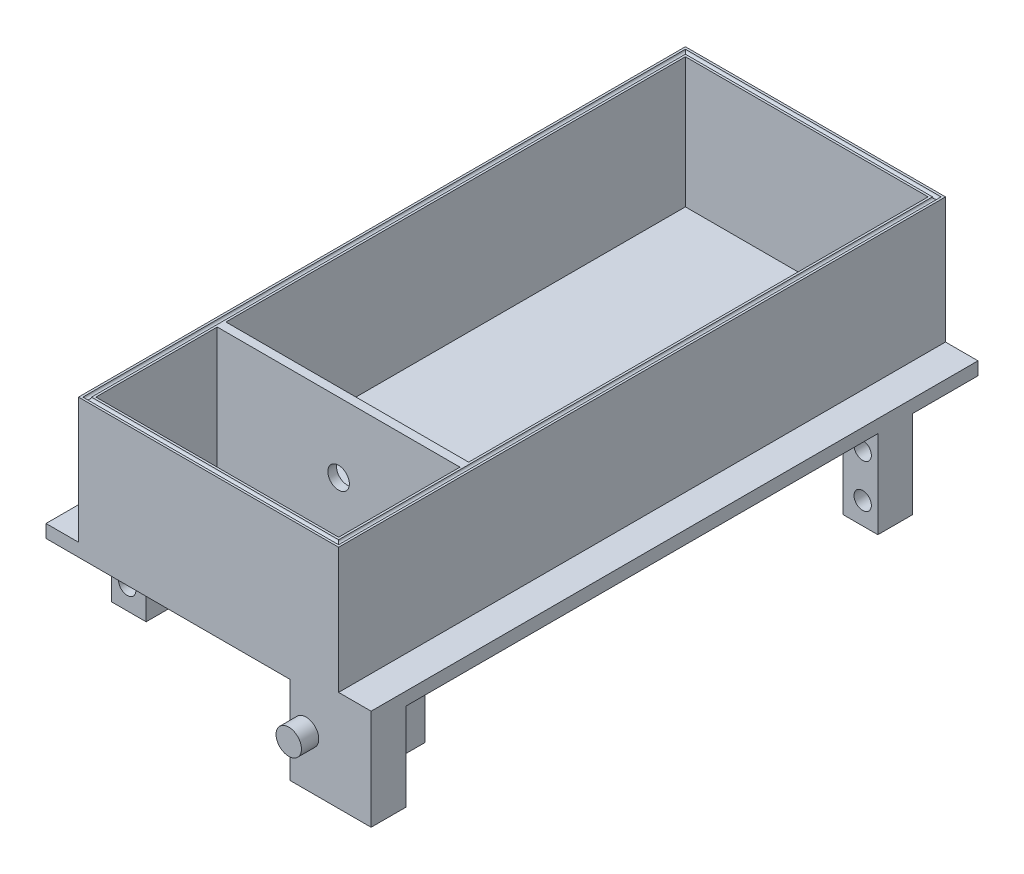
SolidWorks part; units mm, degrees
ref_plane "Front Plane" through (0, 0, 0) normal (0, 0, 1) x (1, 0, 0)
ref_plane "Top Plane" through (0, 0, 0) normal (0, 1, 0) x (1, 0, 0)
ref_plane "Right Plane" through (0, 0, 0) normal (1, 0, 0) x (0, 0, -1)
sketch "Sketch1" plane through (0, 0, 0) normal (0, 1, 0) x (1, 0, 0)
  line L1 (-30, 55) -> (30, 55)
  line L2 (-30, 55) -> (-30, -55)
  line L3 (-30, -55) -> (30, -55)
  line L4 (30, 55) -> (30, -55)
  line L5 (-30, 55) -> (30, -55) construction
  line L6 (-30, -55) -> (30, 55) construction
  point P0 (0, 0)
  dimension "D1" = 110
  dimension "D2" = 60
extrude "Boss-Extrude1" add sketch "Sketch1" along normal blind 2
sketch "Sketch2" plane through (0, 2, 0) normal (0, 1, 0) x (1, 0, 0)
  line L0 (-28, 53) -> (-28, -53)
  line L1 (-28, -53) -> (28, -53)
  line L2 (28, -53) -> (28, 53)
  line L3 (28, 53) -> (-28, 53)
  line L4 (30, -55) -> (30, 55)
  line L5 (30, 55) -> (-30, 55)
  line L6 (-30, 55) -> (-30, -55)
  line L7 (-30, -55) -> (30, -55)
  line L8 (30, -55) -> (30, 55)
  line L9 (30, 55) -> (-30, 55)
  line L10 (-30, 55) -> (-30, -55)
  line L11 (-30, -55) -> (30, -55)
  dimension "D1" = 0
  dimension "D2" = 2
extrude "Boss-Extrude2" add sketch "Sketch2" along normal blind 30
sketch "Sketch3" plane through (0, 0, 0) normal (0, 1, 0) x (1, 0, 0)
  line L0 (-30, -55) -> (30, -55) construction
  line L1 (-30, -55) -> (30, -55)
  line L2 (-30, -55) -> (-30, -85)
  line L3 (-30, -85) -> (30, -85)
  line L4 (30, -55) -> (30, -85)
  line L5 (30, -55) -> (30, 55) construction
  line L6 (-30, 55) -> (-30, -55) construction
  dimension "D2" = 30
extrude "Boss-Extrude3" add sketch "Sketch3" along normal blind 2
sketch "Sketch4" plane through (0, 2, 0) normal (0, 1, 0) x (1, 0, 0)
  line L4 (-28, -55) -> (-30, -55)
  line L8 (-28, -57) -> (-28, -83)
  line L9 (-28, -83) -> (28, -83)
  line L10 (28, -83) -> (28, -57)
  line L11 (28, -57) -> (-28, -57)
  line L12 (-28, -55) -> (-28, -83)
  line L13 (-28, -83) -> (28, -83)
  line L14 (28, -83) -> (28, -55)
  line L16 (-30, -55) -> (-30, -85)
  line L17 (-30, -85) -> (30, -85)
  line L18 (30, -85) -> (30, -55)
  line L19 (30, -55) -> (-30, -55)
  line L20 (-30, -55) -> (-30, -85)
  line L21 (-30, -85) -> (30, -85)
  line L22 (30, -85) -> (30, -55)
  line L23 (30, -55) -> (28, -55)
  dimension "D1" = 2
  dimension "D2" = 0
extrude "Boss-Extrude4" add sketch "Sketch4" along normal blind 30
sketch "Sketch5" plane through (0, 0, 55) normal (0, 0, 1) x (1, 0, 0)
  circle A0 centre (0, 15.8909) radius 2.4868
extrude "Cut-Extrude1" cut sketch "Sketch5" against normal blind 30
sketch "Sketch6" plane through (0, 32, 0) normal (0, 1, 0) x (1, 0, 0)
  line L17 (-29, 54) -> (-29, -84)
  line L18 (-29, -84) -> (29, -84)
  line L19 (29, -84) -> (29, 54)
  line L22 (29, 54) -> (-29, 54)
  line L25 (-29, 54) -> (-29, -84)
  line L26 (-29, -84) -> (29, -84)
  line L27 (29, -84) -> (29, 54)
  line L30 (29, 54) -> (-29, 54)
  dimension "D1" = 1
sweep "Cut-Sweep1" cut path "Sketch6" circular profile diameter 1 parameters "D3"=1
sketch "Sketch43" plane through (0, 0, 0) normal (0, -1, 0) x (1, 0, 0)
  line L11 (30, -55) -> (37.5, -55)
  line L12 (37.5, -55) -> (37.5, 85)
  line L13 (37.5, 85) -> (30, 85)
  line L14 (-30, -55) -> (-37.5, -55)
  line L15 (-37.5, -55) -> (-37.5, 85)
  line L16 (-37.5, 85) -> (-30, 85)
  line L18 (-30, 55) -> (-30, -55)
  line L19 (-30, 55) -> (-30, 85)
  line L21 (30, -55) -> (30, 85)
  dimension "D1" = 7.5
  dimension "D2" = 7.5
extrude "Boss-Extrude7" add sketch "Sketch43" against normal blind 3 contours L13 L21 L11 L12 | L16 L19 L18 L14 L15
sketch "Sketch55" plane through (0, 0, 0) normal (0, -1, 0) x (1, 0, 0)
  line L0 (-37.5, 85) -> (37.5, 85) construction
  line L1 (-37.5, 69.9) -> (-29.5, 69.9)
  line L2 (-37.5, 69.9) -> (-37.5, 61.9)
  line L3 (-37.5, 61.9) -> (-29.5, 61.9)
  line L4 (-29.5, 69.9) -> (-29.5, 61.9)
  line L6 (10.5, 69.9) -> (10.5, 61.9)
  line L9 (37.5, -55) -> (-37.5, -55) construction
  line L10 (37.5, -39.9) -> (29.5, -39.9)
  line L11 (37.5, -39.9) -> (37.5, -31.9)
  line L12 (37.5, -31.9) -> (29.5, -31.9)
  line L13 (29.5, -39.9) -> (29.5, -31.9)
  line L15 (-10.5, -39.9) -> (-10.5, -31.9)
  line L20 (-10.5, -39.9) -> (-18.5, -39.9)
  line L21 (-18.5, -39.9) -> (-18.5, -55)
  line L22 (-18.5, -55) -> (-37.5, -55)
  line L23 (-37.5, -55) -> (-37.5, -47)
  line L24 (-37.5, -55) -> (-37.5, 85) construction
  line L25 (-37.5, -47) -> (-26.5, -47)
  line L26 (-26.5, -47) -> (-26.5, -31.9)
  line L27 (-26.5, -31.9) -> (-10.5, -31.9)
  line L28 (10.5, 69.9) -> (18.782, 69.9)
  line L29 (18.782, 69.9) -> (18.782, 85)
  line L30 (18.782, 85) -> (37.5, 85)
  line L33 (37.5, 85) -> (37.5, 77)
  line L34 (37.5, -55) -> (37.5, 85) construction
  line L35 (37.5, 77) -> (26.782, 77)
  line L37 (26.782, 77) -> (26.782, 61.9)
  line L38 (26.782, 61.9) -> (10.5, 61.9)
  dimension "D1" = 8
  dimension "D2" = 8
  dimension "D3" = 8
  dimension "D4" = 15.1
  dimension "D5" = 40
  dimension "D6" = 8
  dimension "D7" = 8
  dimension "D8" = 8
  dimension "D9" = 8
  dimension "D10" = 40
  dimension "D11" = 8
  dimension "D12" = 8
  dimension "D13" = 15.1
  dimension "D14" = 8
  dimension "D15" = 8
extrude "Boss-Extrude10" add sketch "Sketch55" along normal blind 20.2
sketch "Sketch56" plane through (0, 0, 85) normal (0, 0, 1) x (1, 0, 0)
  line L1 (-9.359, 0) -> (-9.359, -17.0658) construction
  line L4 (-33.859, -15.1) -> (-33.859, -5.1) construction
  line L6 (-37.5, 0) -> (18.782, 0) construction
  circle A0 centre (-33.859, -15.1) radius 2
  circle A1 centre (-33.859, -5.1) radius 2
  circle A2 centre (15.141, -15.1) radius 2
  circle A3 centre (15.141, -5.1) radius 2
  dimension "D1" = 4
  dimension "D2" = 4
  dimension "D3" = 10
  dimension "D4" = 49
  dimension "D5" = 24.5
extrude "Cut-Extrude3" cut sketch "Sketch56" against normal blind 46.2
sketch "Sketch59" plane through (0, 0, -55) normal (0, 0, -1) x (-1, 0, 0)
  line L0 (-34, -5.1) -> (-34, -15.1) construction
  line L1 (-9.5, 0) -> (-9.5, -20.2) construction
  line L5 (-37.5, 0) -> (18.5, 0) construction
  circle A0 centre (-34, -15.1) radius 2
  circle A1 centre (-34, -5.1) radius 2
  circle A2 centre (15, -5.1) radius 2
  circle A3 centre (15, -15.1) radius 2
  dimension "D2" = 4
  dimension "D3" = 4
  dimension "D1" = 10
  dimension "D4" = 24.5
extrude "Cut-Extrude4" cut sketch "Sketch59" against normal blind 49.2
sketch "Sketch60" plane through (0, 0, -55) normal (0, 0, -1) x (-1, 0, 0)
  line L0 (37.5, 3) -> (37.5, -20.2) construction
  line L1 (30, 3) -> (-30, 3) construction
  line L2 (22.5, 3) -> (22.5, -8.6) construction
  line L3 (22.5, -8.6) -> (22.5, -20.2) construction
  line L4 (37.5, -20.2) -> (10.5, -20.2) construction
  circle A0 centre (22.5, -8.6) radius 2.925
  dimension "D1" = 5.85
  dimension "D2" = 15
extrude "Boss-Extrude11" add sketch "Sketch60" along normal blind 4
sketch "Sketch61" plane through (0, 0, 85) normal (0, 0, 1) x (1, 0, 0)
  line L0 (30, 3) -> (-30, 3) construction
  line L1 (22.5, -8.6) -> (22.5, 3) construction
  line L2 (22.5, -8.6) -> (22.5, -20.2) construction
  line L3 (37.5, -20.2) -> (10.5, -20.2) construction
  line L4 (37.5, 3) -> (37.5, -20.2) construction
  circle A0 centre (22.5, -8.6) radius 2.925
  dimension "D1" = 5.85
  dimension "D2" = 15
extrude "Boss-Extrude12" add sketch "Sketch61" along normal blind 4
